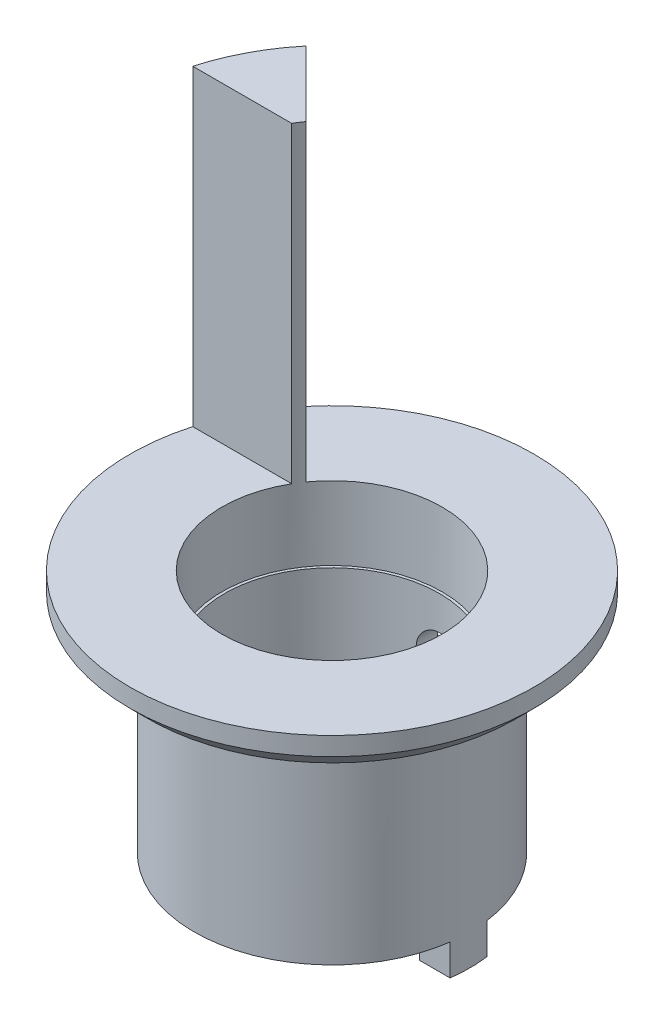
SolidWorks part; units mm, degrees
material "2024-T4"
ref_plane "Спереди" through (0, 0, 0) normal (0, 0, 1) x (1, 0, 0)
ref_plane "Сверху" through (0, 0, 0) normal (0, 1, 0) x (1, 0, 0)
ref_plane "Справа" through (0, 0, 0) normal (1, 0, 0) x (0, 0, -1)
sketch "Эскиз1" plane through (0, 0, 0) normal (0, 0, 1) x (1, 0, 0)
  line L0 (0, 0) -> (0, 27.7091) construction
  line L1 (5.85, 0) -> (5.85, 11)
  line L4 (6, 32) -> (11, 32)
  line L5 (11, 32) -> (11, 13)
  line L6 (11, 13) -> (7.5, 13)
  line L7 (7.5, 13) -> (7.5, 0)
  line L8 (7.5, 0) -> (5.85, 0)
  line L9 (5.85, 11) -> (6, 11)
  line L10 (6, 11) -> (6, 32)
  dimension "D1" = 11.7
  dimension "D3" = 13
  dimension "D4" = 32
  dimension "D6" = 15
  dimension "D7" = 22
  dimension "D8" = 12
  dimension "D9" = 21
revolve "Повернуть1" add sketch "Эскиз1" angle 360 about L0
sketch "Эскиз2" plane through (0, 32, 0) normal (0, 1, 0) x (1, 0, 0)
  line L0 (-10.583, 3) -> (-5.1962, 3)
  line L1 (-4.8904, 3.4762) -> (-5.1962, 3)
  line L3 (-8.4531, 7.0389) -> (-4.8904, 3.4762)
  circle A0 centre (0, 0) radius 11 construction
  circle A4 centre (0, 0) radius 6 construction
  circle M2 centre (0, 0) radius 11
  dimension "D1" = 3
  dimension "D3" = 1
  dimension "D2" = 45
extrude "Вырез-Вытянуть2" cut sketch "Эскиз2" against normal blind 17 contours L3 L0 M2 region at (-7.8896, 32, -2.6889) region at (0.0001, 32, 0.0001)
sketch "Эскиз3" plane through (0, 15, 0) normal (0, 1, 0) x (1, 0, 0)
  line L0 (-0.3866, 10.9932) -> (7.5, 3.1066)
  line L1 (7.5, -3.1066) -> (-0.3866, -10.9932)
  line L2 (-8.4531, 7.0389) -> (-4.8904, 3.4762) construction
  line L3 (7.5, 3.1066) -> (7.5, -3.1066)
  arc A2 (-10.583, 3) -> (-8.4531, 7.0389) centre (0, 0) ccw construction
  circle A3 centre (0, 0) radius 7.5 construction
  dimension "D1" = 45
extrude "Вырез-Вытянуть3" [suppressed] cut sketch "Эскиз3" against normal through all
chamfer "Фаска1" distance 1 angle 45 1 edges at (0, 13, -11)
sketch "Эскиз5" plane through (0, 0, 0) normal (0, -1, 0) x (1, 0, 0)
  line L0 (0, 0) -> (3.9543, 1)
  line L1 (0, 0) -> (3.9553, -1)
  line L3 (3.9543, 1) -> (7.433, 1)
  line L4 (3.9553, -1) -> (7.433, -1)
  circle A0 centre (0, 0) radius 7.5 construction
  arc A1 (7.433, 1) -> (7.433, -1) centre (0, 0) cw
  dimension "D1" = 1
  dimension "D2" = 2
extrude "Вырез-Вытянуть4" cut sketch "Эскиз5" against normal blind 1.7 flip side to cut
sketch "Эскиз6" plane through (0, 0, 0) normal (1, 0, 0) x (0, 0, -1)
  line L0 (7.5, 10.5) -> (7, 10.5)
  line L1 (7.5, 1.7) -> (7.5, 13) construction
  line L2 (7, 10.5) -> (7, 5.5)
  line L3 (7, 5.5) -> (7.5, 5.5)
  line L4 (-7.5, 1.7) -> (7.5, 1.7) construction
  dimension "D1" = 5
  dimension "D2" = 3.8
  dimension "D3" = 7
extrude "Вырез-Вытянуть5" cut sketch "Эскиз6" against normal through all and the other way through all
hole_wizard "Диаметр отверстия Ø2.3 (2.3)1" positions "Трехмерный эскиз1" profile "Эскиз4" hole size "Ø2.3" standard "Ansi (метрические)" end condition up to next
sketch3d "Трехмерный эскиз1"
  point P0 (0, 8, -7)
  dimension "D1" = 8
sketch "Эскиз4" plane through (0, 8, -7) normal (1, 0, 0) x (0, 1, 0)
  line L0 (0, 0) -> (0, 1.15)
  line L1 (0, 1.15) -> (1.15, 1.15)
  line L2 (1.15, 1.15) -> (1.15, 0.1)
  line L3 (1.15, 0.1) -> (1.25, 0)
  line L5 (1.25, 0) -> (0, 0)
  line L6 (-1.15, 0.1) -> (-1.25, 0) construction
  line L11 (0, -6.35) -> (0, 107.95) construction
  dimension "Диаметр сквозного отверстия" = 2.3
  dimension "Глубина сквозного отверстия" = 1.15
  dimension "Диаметр передней зенковки" = 2.5
  dimension "Угол передней зенковки" = 90
